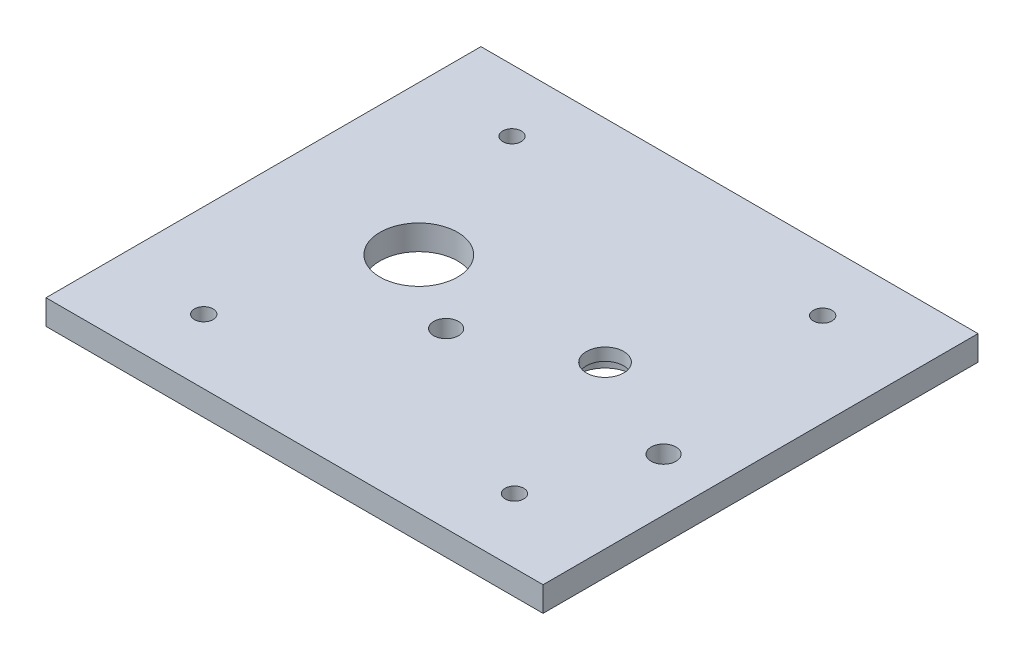
SolidWorks part; units mm, degrees
ref_plane "Front Plane" through (0, 0, 0) normal (0, 0, 1) x (1, 0, 0)
ref_plane "Top Plane" through (0, 0, 0) normal (0, 1, 0) x (1, 0, 0)
ref_plane "Right Plane" through (0, 0, 0) normal (1, 0, 0) x (0, 0, -1)
sketch "Sketch1" plane through (0, 0, 0) normal (0, 1, 0) x (1, 0, 0)
  line L0 (0, 8.2993) -> (0, -7.906) construction
  line L1 (-40, 35) -> (40, 35)
  line L2 (-40, 35) -> (-40, -35)
  line L3 (-40, -35) -> (40, -35)
  line L4 (40, 35) -> (40, -35)
  line L5 (-40, 35) -> (40, -35) construction
  line L6 (-40, -35) -> (40, 35) construction
  line L7 (-14.9915, 0.1967) -> (11.9413, 0.1967) construction
  line L9 (35.0085, 0.1967) -> (61.9413, 0.1967) construction
  line L11 (12.5001, 2.9838) -> (12.5001, -1.0162)
  line L13 (15.4999, 3.0162) -> (15.4999, -0.9838)
  line L14 (12.5001, 2.9838) -> (15.4999, -0.9838) construction
  line L15 (12.5001, -1.0162) -> (15.4999, 3.0162) construction
  circle A0 centre (-25, 25) radius 1.5
  circle A1 centre (25, 25) radius 1.5
  circle A2 centre (25, -24.6067) radius 1.5
  circle A3 centre (-25, -24.6067) radius 1.5
  circle A4 centre (14, 1) radius 10
  circle A5 centre (-16, 1) radius 20
  arc A6 (12.5001, 2.9838) -> (15.4999, 3.0162) centre (14.0217, 1.0001) cw
  arc A7 (12.5001, -1.0162) -> (15.4999, -0.9838) centre (13.9783, 0.9999) ccw
  circle A8 centre (13.9783, 0.9999) radius 4.5
  circle A9 centre (14, -6) radius 14
  circle A10 centre (-3.5, -7.1027) radius 2
  circle A11 centre (31.5, -7.1027) radius 2
  circle A12 centre (-16, 1) radius 6.25
  circle A13 centre (13.9783, 0.9999) radius 3
  point P0 (0, 0)
  dimension "D3" = 15
  dimension "D6" = 3
  dimension "D7" = 26
  dimension "D10" = 20
  dimension "D11" = 9
  dimension "D12" = 7
  dimension "D13" = 17.5
  dimension "D14" = 4
  dimension "D15" = 4
  dimension "D17" = 40
  dimension "D20" = 12.5
  dimension "D21" = 6
  dimension "D1" = 80
  dimension "D2" = 70
  dimension "D4" = 10
  dimension "D8" = 4
  dimension "D9" = 3
  dimension "D16" = 17.5
  dimension "D18" = 36
  dimension "D19" = 4
  dimension "D5" = 2
extrude "Boss-Extrude4" add sketch "Sketch1" along normal blind 4 contours L4 L1 L2 L3 A11 A9 A4 A5 A2 A1 A0 A3 | A9 A5 A10 | A9 A4 | A5 A9 A4 | A5 A9 | A4 A9 A8 | A8 A13 | A4 A9 A5 region at (0, 0, -33.937) region at (4.4048, 0, -2.6588) region at (4.1111, 0, -3.2378) region at (1.9776, 0, 3.1948) region at (15.1814, 0, 11.2492) region at (14, 0, -8.4705) region at (-0.1835, 0, 2.6905) region at (9.6056, 0, -0.9999)
sketch "Sketch2" plane through (0, 4, 0) normal (0, 1, 0) x (1, 0, 0)
  circle A3 centre (-16, 1) radius 11.25
  circle A4 centre (-16, 1) radius 11.25
  dimension "D1" = 5
extrude "Cut-Extrude2" cut sketch "Sketch1<7>" along normal blind 2 contours A8
sketch "Sketch1<7>" plane through (0, 0, 0) normal (0, 1, 0) x (1, 0, 0) same geometry as "Sketch1"
